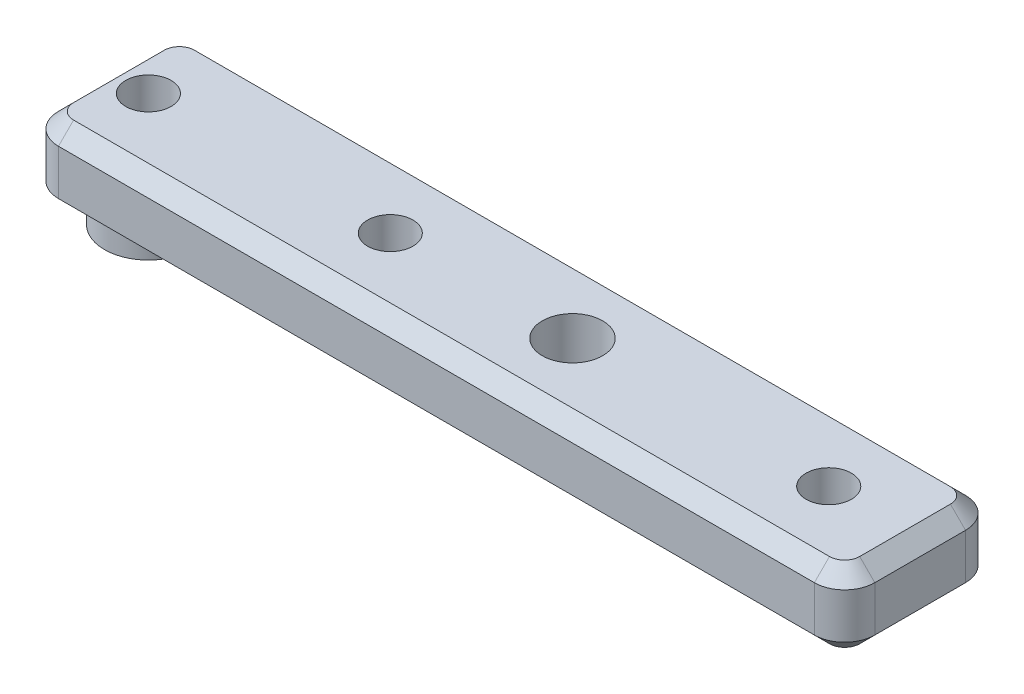
SolidWorks part; units mm, degrees
ref_plane "Front Plane" through (0, 0, 0) normal (0, 0, 1) x (1, 0, 0)
ref_plane "Top Plane" through (0, 0, 0) normal (0, 1, 0) x (1, 0, 0)
ref_plane "Right Plane" through (0, 0, 0) normal (1, 0, 0) x (0, 0, -1)
sketch "Sketch1" plane through (0, 0, 0) normal (0, 1, 0) x (1, 0, 0)
  line L1 (-27, 5) -> (27, 5)
  line L2 (-27, 5) -> (-27, -5)
  line L3 (-27, -5) -> (27, -5)
  line L4 (27, 5) -> (27, -5)
  line L5 (-27, 5) -> (27, -5) construction
  line L6 (-27, -5) -> (27, 5) construction
  point P0 (0, 0)
  dimension "D1" = 54
  dimension "D2" = 10
extrude "Boss-Extrude1" add sketch "Sketch1" along normal blind 5
sketch "Sketch3" plane through (0, 5, 0) normal (0, 1, 0) x (1, 0, 0)
  circle A0 centre (-24.05, 0) radius 1.5
  circle A1 centre (4, 0) radius 2
  circle A3 centre (-8.05, 0) radius 1.5
  circle A4 centre (20.95, 0) radius 1.5
  dimension "D3" = 3
  dimension "D4" = 4
  dimension "D7" = 3
  dimension "D9" = 3
  dimension "D1" = 28.05
  dimension "D2" = 4
  dimension "D8" = 16
  dimension "D10" = 29
extrude "Cut-Extrude1" cut sketch "Sketch3" against normal blind 7
fillet "Fillet1" radius 2 4 edges at (27, 2.5, -5) (-27, 2.5, -5) (27, 2.5, 5) (-27, 2.5, 5)
sketch "Sketch4" plane through (0, 0, 0) normal (0, -1, 0) x (1, 0, 0)
  circle A0 centre (-24.05, 0) radius 1.5
  circle A1 centre (-24.05, 0) radius 2.9
  dimension "D1" = 1.4
extrude "Boss-Extrude2" add sketch "Sketch4" along normal blind 2.5
chamfer "Chamfer1" distance 1 angle 45 16 edges at (0, 0, -5) (-26.4142, 0, -4.4142) (-27, 0, 0) (-26.4142, 0, 4.4142) (0, 0, 5) (0, 5, -5) (-26.4142, 5, -4.4142) (-27, 5, 0) (-26.4142, 5, 4.4142) (0, 5, 5) (26.4142, 0, -4.4142) (27, 0, 0) (26.4142, 0, 4.4142) (26.4142, 5, -4.4142) (27, 5, 0) (26.4142, 5, 4.4142)
